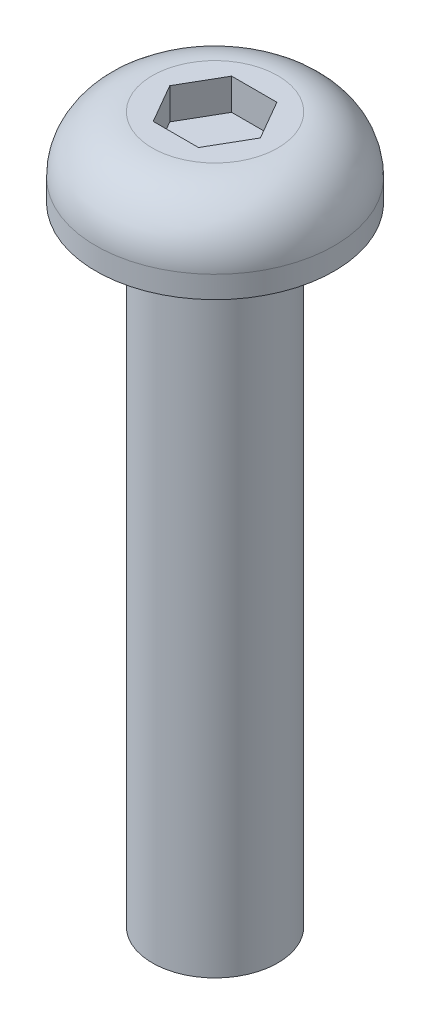
SolidWorks part; units mm, degrees
ref_plane "Front Plane" through (0, 0, 0) normal (0, 0, 1) x (1, 0, 0)
ref_plane "Top Plane" through (0, 0, 0) normal (0, 1, 0) x (1, 0, 0)
ref_plane "Right Plane" through (0, 0, 0) normal (1, 0, 0) x (0, 0, -1)
sketch "Sketch1" plane through (0, 0, 0) normal (0, 0, 1) x (1, 0, 0)
  line L0 (2, 0) -> (3.8, 0)
  line L1 (3.8, 0) -> (3.8, 0.7)
  line L2 (2, 2.5) -> (0, 2.5)
  line L3 (2, 0) -> (2, -20)
  line L4 (2, -20) -> (0, -20)
  line L5 (0, -20) -> (0, 2.5)
  arc A0 (3.8, 0.7) -> (2, 2.5) centre (2, 0.7) ccw
  dimension "D1" = 2
  dimension "D2" = 20
  dimension "D3" = 3.8
  dimension "D4" = 2.5
revolve "Revolve1" add sketch "Sketch1" angle 360 about L5
sketch "Sketch2" plane through (0, 2.5, 0) normal (0, 1, 0) x (1, 0, 0)
  line L1 (0.7217, 1.25) -> (-0.7217, 1.25)
  line L2 (-0.7217, 1.25) -> (-1.4434, 0)
  line L3 (-1.4434, 0) -> (-0.7217, -1.25)
  line L4 (-0.7217, -1.25) -> (0.7217, -1.25)
  line L5 (0.7217, -1.25) -> (1.4434, 0)
  line L6 (1.4434, 0) -> (0.7217, 1.25)
  circle A0 centre (0, 0) radius 1.25 construction
  point P1 (-0.7217, 1.25)
  dimension "D1" = 2.5
extrude "Cut-Extrude1" cut sketch "Sketch2" against normal blind 1
